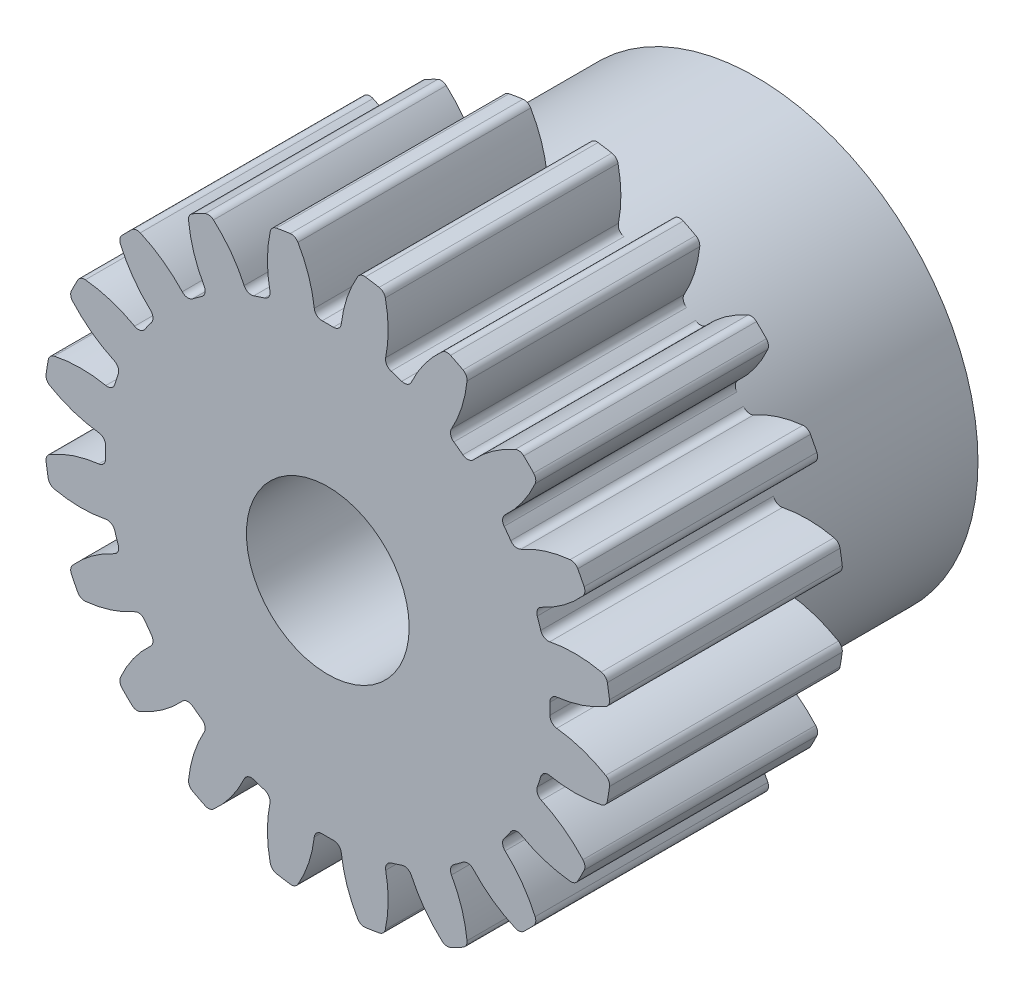
SolidWorks part; units mm, degrees
material "Cast Alloy Steel"
ref_plane "Front Plane" through (0, 0, 0) normal (0, 0, 1) x (1, 0, 0)
ref_plane "Top Plane" through (0, 0, 0) normal (0, 1, 0) x (1, 0, 0)
ref_plane "Right Plane" through (0, 0, 0) normal (1, 0, 0) x (0, 0, -1)
sketch "Sketch1" plane through (0, 0, 0) normal (0, 0, 1) x (1, 0, 0)
  circle A0 centre (0, 0) radius 7.938
  circle A1 centre (0, 0) radius 8.7318
  circle A2 centre (0, 0) radius 6.8267
  circle A3 centre (0, 0) radius 2.5
  dimension "D1" = 15.876
  dimension "D2" = 17.4636
  dimension "D4" = 5
  dimension "D3" = 1.9051
extrude "Boss-Extrude2" add sketch "Sketch1" along normal blind 7.15 contours A2 A3 | A0 A2 | A1 A0 region at (-7.7135, 0, 0) region at (-8.4848, 0, 0) region at (-6.6336, 0, 0)
extrude "Boss-Extrude3" add sketch "Sketch1<5>" against normal blind 6 contours A2 A3 region at (-6.6336, 0, 0)
sketch "Sketch1<5>" plane through (0, 0, 0) normal (0, 0, 1) x (1, 0, 0) same geometry as "Sketch1"
sketch "Sketch4" plane through (0, 0, 7.15) normal (0, 0, 1) x (1, 0, 0)
  line L0 (0, 0) -> (0, 8.7318) construction
  line L1 (0.6228, 7.9135) -> (-0.6228, 7.9135) construction
  line L2 (0, 0) -> (0.3961, 6.8152) construction
  line L3 (0, 6.2024) -> (1.255, 9.6505) construction
  line L4 (0, 0) -> (-1.366, 8.6243) construction
  line L5 (-0.6228, 7.9135) -> (-1.8531, 7.7187) construction
  arc A1 (0.3961, 6.8152) -> (1.7866, 9.5664) centre (4.257, 6.5908) cw
  arc A2 (-0.3961, 6.8152) -> (-1.7866, 9.5664) centre (-4.257, 6.5908) ccw
  circle A3 centre (0, 0) radius 6.8267 construction
  arc A4 (0.3961, 6.8152) -> (-0.3961, 6.8152) centre (0, 0) ccw
  circle A5 centre (0, 0) radius 8.7318 construction
  circle A6 centre (0, 0) radius 7.938 construction
  circle A7 centre (0, 0) radius 8.7318 construction
  circle A10 centre (0, 0) radius 9.7318
  arc A11 (1.7866, 9.5664) -> (-1.7866, 9.5664) centre (0, 0) ccw
  dimension "D2" = 20
  dimension "D3" = 9
extrude "Cut-Extrude1" cut sketch "Sketch4" along normal through all from surface starting at face at (6.8267, 0, 0)
fillet "Fillet1" radius 0.2381 4 edges at (-0.3961, 6.8152, 3.575) (0.3961, 6.8152, 3.575) (-0.9989, 8.6745, 3.575) (0.9989, 8.6745, 3.575)
pattern_circular "CirPattern2" count 20 over 360 about axis through (0, 0, 7.15) along (0, 0, -1) of "Cut-Extrude1", "Fillet1" reverse direction yes
equation "\"Module\"= 0.7938"
equation "\"Numer of theeth\"= 20"
equation "\"D1@Sketch1\"=\"Module\" * \"Numer of theeth\""
equation "\"D2@Sketch1\"=(\"Numer of theeth\" + 2) * \"Module\""
equation "\"D3@Sketch1\"=\"Module\" * if( \"Module\" =>1.25,2.25,2.4)"
equation "\"pressure angle\"= 20deg"
equation "\"D2@Sketch4\"=\"pressure angle\""
equation "\"D3@Sketch4\"=180 / \"Numer of theeth\""
equation "\"D1@Fillet1\"=.3 * \"Module\""
equation "\"D1@CirPattern2\"=\"Numer of theeth\""
